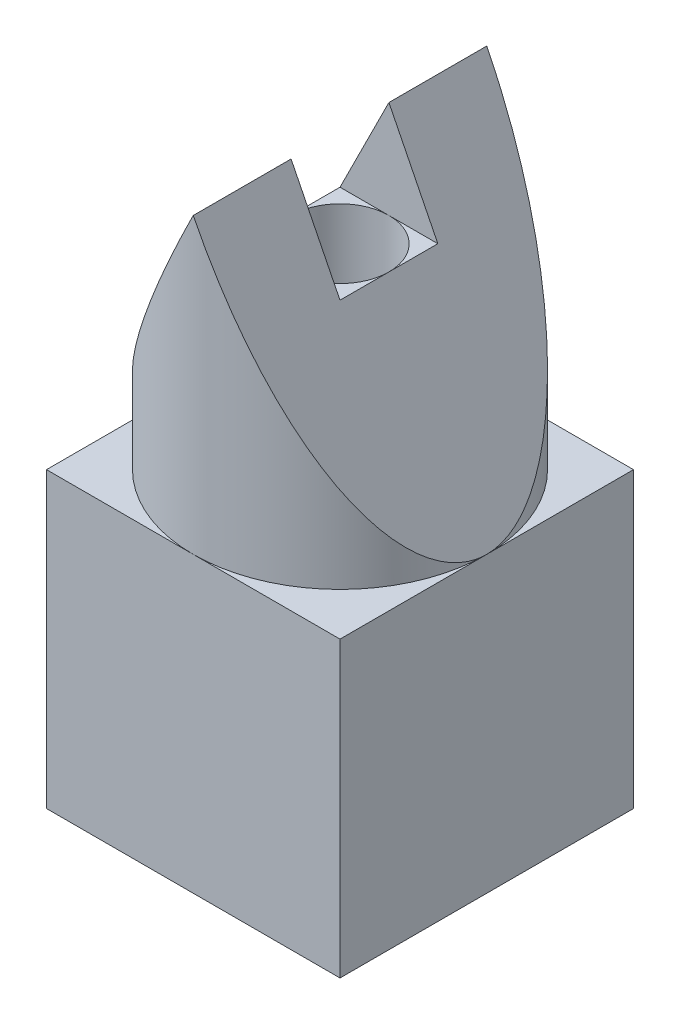
SolidWorks part; units mm, degrees
ref_plane "Front Plane" through (0, 0, 0) normal (0, 0, 1) x (1, 0, 0)
ref_plane "Top Plane" through (0, 0, 0) normal (0, 1, 0) x (1, 0, 0)
ref_plane "Right Plane" through (0, 0, 0) normal (1, 0, 0) x (0, 0, -1)
sketch "Sketch1" plane through (0, 0, 0) normal (0, 1, 0) x (1, 0, 0)
  line L0 (0, 49.6154) -> (0, -49.6154) construction
  line L1 (-35.5385, 0) -> (35.5385, 0) construction
  line L3 (-30, -30) -> (30, -30)
  line L4 (-30, -30) -> (-30, 30)
  line L5 (-30, 30) -> (30, 30)
  line L6 (30, -30) -> (30, 30)
  line L7 (-30, -30) -> (30, 30) construction
  line L8 (-30, 30) -> (30, -30) construction
  line L9 (-10, -10) -> (10, -10)
  line L10 (-10, -10) -> (-10, 10)
  line L11 (-10, 10) -> (10, 10)
  line L12 (10, -10) -> (10, 10)
  line L13 (-10, -10) -> (10, 10) construction
  line L14 (-10, 10) -> (10, -10) construction
  circle A0 centre (0, 0) radius 10
  circle A1 centre (0, 0) radius 30
  dimension "D1" = 20
  dimension "D2" = 60
extrude "Boss-Extrude1" add sketch "Sketch1" along normal blind 60 contours L4 L5 L6 L3
extrude "Boss-Extrude2" add sketch "Sketch1<3>" along normal blind 120 contours A1
sketch "Sketch1<3>" plane through (0, 0, 0) normal (0, 1, 0) x (1, 0, 0) same geometry as "Sketch1"
extrude "Cut-Extrude1" cut sketch "Sketch1<4>" against normal blind 20 from surface contours L9 L12 L11 L10 starting at face at (0, 120, 30)
sketch "Sketch1<4>" plane through (0, 0, 0) normal (0, 1, 0) x (1, 0, 0) same geometry as "Sketch1"
extrude "Cut-Extrude2" cut sketch "Sketch1<5>" along normal through all contours A0
sketch "Sketch1<5>" plane through (0, 0, 0) normal (0, 1, 0) x (1, 0, 0) same geometry as "Sketch1"
sketch "Sketch2" plane through (0, 0, 30) normal (0, 0, 1) x (1, 0, 0)
  line L0 (0, -4.0181) -> (0, 120) construction
  line L1 (30, 120) -> (-30, 120) construction
  line L2 (-30, 60) -> (0, 120)
  line L3 (0, 120) -> (30, 60)
extrude "Cut-Extrude3" cut sketch "Sketch2" against normal through all and the other way through all contours L2 L3
